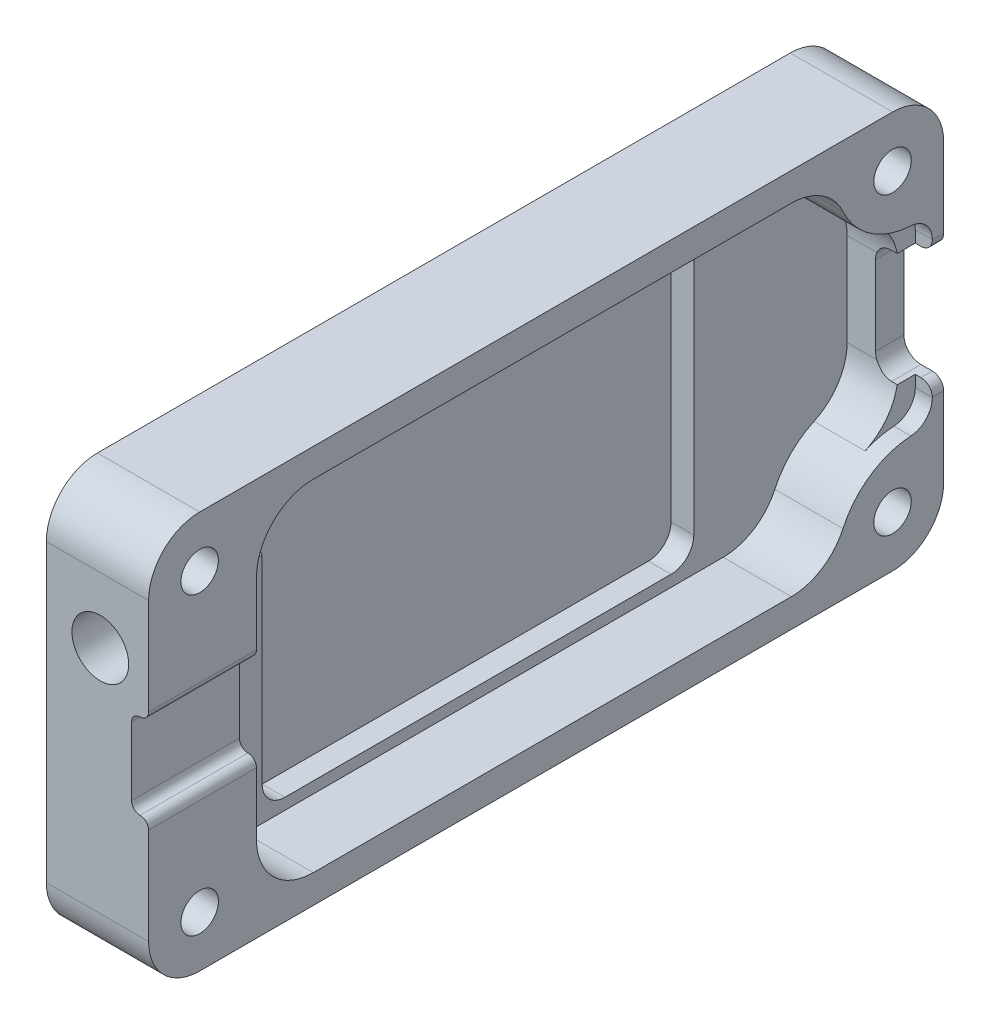
SolidWorks part; units mm, degrees
ref_plane "Front Plane" through (0, 0, 0) normal (0, 0, 1) x (1, 0, 0)
ref_plane "Top Plane" through (0, 0, 0) normal (0, 1, 0) x (1, 0, 0)
ref_plane "Right Plane" through (0, 0, 0) normal (1, 0, 0) x (0, 0, -1)
sketch "Sketch3" plane through (0, 0, 0) normal (1, 0, 0) x (0, 0, -1)
  line L1 (-35, -17.5) -> (35, -17.5)
  line L2 (-35, -17.5) -> (-35, 17.5)
  line L3 (-35, 17.5) -> (35, 17.5)
  line L4 (35, -17.5) -> (35, 17.5)
  line L5 (-35, -17.5) -> (35, 17.5) construction
  line L6 (-35, 17.5) -> (35, -17.5) construction
  point P0 (0, 0)
  dimension "D1" = 70
  dimension "D2" = 35
extrude "Boss-Extrude2" add sketch "Sketch3" along normal blind 3
sketch "Sketch4" plane through (3, 0, 0) normal (1, 0, 0) x (0, 0, -1)
  line L0 (35, 17.5) -> (-35, 17.5) construction
  line L1 (-35, -17.5) -> (35, -17.5)
  line L2 (-35, -17.5) -> (-35, 17.5)
  line L3 (-35, 17.5) -> (35, 17.5)
  line L4 (35, -17.5) -> (35, 17.5)
  line L5 (-35, -17.5) -> (35, 17.5) construction
  line L6 (-35, 17.5) -> (35, -17.5) construction
  line L8 (-32.5, -15) -> (32.5, -15)
  line L9 (-32.5, -15) -> (-32.5, 15)
  line L10 (-32.5, 15) -> (32.5, 15)
  line L11 (32.5, -15) -> (32.5, 15)
  line L12 (-32.5, -15) -> (32.5, 15) construction
  line L13 (-32.5, 15) -> (32.5, -15) construction
  point P0 (0, 0)
  point P8 (0, 0)
  dimension "D1" = 30
  dimension "D2" = 65
  dimension "D3" = 70
extrude "Boss-Extrude3" add sketch "Sketch4" along normal blind 6
sketch "Sketch6" plane through (3, 0, 0) normal (1, 0, 0) x (0, 0, -1)
  line L1 (-32.5, 15) -> (-32.5, -15) construction
  line L2 (32.5, 15) -> (-32.5, 15) construction
  line L3 (-25.5, 15) -> (-32.5, 15)
  line L4 (-32.5, 15) -> (-32.5, 8)
  line L5 (-32.5, -15) -> (32.5, -15) construction
  line L6 (32.5, -15) -> (32.5, 15) construction
  line L7 (-32.5, 15) -> (-32.5, -15) construction
  line L8 (-32.5, -8) -> (-32.5, -15)
  line L9 (-32.5, -15) -> (-25.5, -15)
  line L10 (-32.5, -15) -> (32.5, -15) construction
  line L11 (32.5, 8) -> (32.5, 15)
  line L12 (32.5, 15) -> (25.5, 15)
  line L13 (32.5, -8) -> (32.5, -15)
  line L14 (32.5, -15) -> (25.5, -15)
  arc A0 (-32.5, 8) -> (-25.5, 15) centre (-32.5, 15) ccw
  arc A1 (-32.5, -8) -> (-25.5, -15) centre (-32.5, -15) cw
  arc A2 (32.5, -8) -> (25.5, -15) centre (32.5, -15) ccw
  arc A3 (25.5, 15) -> (32.5, 8) centre (32.5, 15) ccw
  dimension "D1" = 7
extrude "Boss-Extrude4" add sketch "Sketch6" along normal blind 6
sketch "Sketch7" plane through (3, 0, 0) normal (1, 0, 0) x (0, 0, -1)
  line L1 (-19, -14) -> (19, -14)
  line L2 (-19, -14) -> (-19, 14)
  line L3 (-19, 14) -> (19, 14)
  line L4 (19, -14) -> (19, 14)
  line L5 (-19, -14) -> (19, 14) construction
  line L6 (-19, 14) -> (19, -14) construction
  point P0 (0, 0)
  dimension "D1" = 38
  dimension "D2" = 28
extrude "Cut-Extrude1" cut sketch "Sketch7" against normal blind 2
sketch "Sketch17" plane through (3, 0, 0) normal (1, 0, 0) x (0, 0, -1)
  line L1 (-25.5, -15) -> (-32.5, -15)
  line L2 (-25.5, -15) -> (-25.5, 15)
  line L3 (-25.5, 15) -> (-32.5, 15)
  line L4 (-32.5, -15) -> (-32.5, 15)
extrude "Boss-Extrude6" add sketch "Sketch17" along normal up to surface (6 mm away) up to face at (9, 0, 0)
sketch "Sketch8" plane through (9, 0, 0) normal (1, 0, 0) x (0, 0, -1)
  line L0 (-35, 17.5) -> (-35, -17.5) construction
  line L1 (-35, -17.5) -> (35, -17.5) construction
  line L2 (35, 17.5) -> (-35, 17.5) construction
  line L3 (35, -17.5) -> (35, 17.5) construction
  circle A0 centre (-30.5, 13) radius 1.65
  circle A1 centre (30.5, 13) radius 1.65
  circle A2 centre (30.5, -13) radius 1.65
  circle A3 centre (-30.5, -13) radius 1.65
  dimension "D3" = 3.3
  dimension "D6" = 4.5
  dimension "D1" = 4.5
  dimension "D2" = 4.5
  dimension "D4" = 4.5
  dimension "D5" = 4.5
  dimension "D7" = 4.5
  dimension "D8" = 4.5
  dimension "D9" = 4.5
extrude "Cut-Extrude2" cut sketch "Sketch8" against normal up to surface (9 mm away) up to face at (0, 0, 0)
fillet "Fillet1" radius 4.5 4 edges at (4.5, -17.5, -35) (4.5, 17.5, -35) (4.5, 17.5, 35) (4.5, -17.5, 35)
sketch "Sketch9" plane through (9, 0, 0) normal (1, 0, 0) x (0, 0, -1)
  line L0 (32.5, -8) -> (32.5, 8) construction
  line L1 (32.5, 5) -> (35, 5)
  line L2 (32.5, 5) -> (32.5, -5)
  line L3 (32.5, -5) -> (35, -5)
  line L4 (35, 5) -> (35, -5)
  line L5 (35, -13) -> (35, 13) construction
  line L6 (30.5, 17.5) -> (-30.5, 17.5) construction
  line L7 (-30.5, -17.5) -> (30.5, -17.5) construction
  dimension "D1" = 12.5
  dimension "D2" = 12.5
extrude "Cut-Extrude3" cut sketch "Sketch9" against normal blind 3.5
sketch "Sketch10" plane through (9, 0, 0) normal (1, 0, 0) x (0, 0, -1)
  line L1 (32.5, 8) -> (34, 8)
  line L2 (32.5, 8) -> (32.5, -8)
  line L3 (32.5, -8) -> (34, -8)
  line L4 (34, 8) -> (34, -8)
  point P7 (32.5, -8)
  dimension "D1" = 1.5
extrude "Cut-Extrude4" cut sketch "Sketch10" against normal blind 1.5
fillet "Fillet2" radius 1 2 edges at (9, -5, -34.5) (9, 5, -34.5)
fillet "Fillet3" radius 1.5 2 edges at (5.5, 5, -33.75) (5.5, -5, -33.75)
sketch "Sketch11" plane through (0, 0, 0) normal (-1, 0, 0) x (0, 0, 1)
  circle A1 centre (30.5, 13) radius 3
  circle A2 centre (30.5, -13) radius 3
  circle A3 centre (-30.5, -13) radius 3
  circle A4 centre (-30.5, 13) radius 3
  dimension "D1" = 6
extrude "Cut-Extrude5" cut sketch "Sketch11" against normal blind 1.8
sketch "Sketch12" plane through (9, 0, 0) normal (1, 0, 0) x (0, 0, -1)
  line L0 (-35, 13) -> (-35, -13) construction
  line L1 (-35, 3.75) -> (-25.5, 3.75)
  line L2 (-35, 3.75) -> (-35, -3.75)
  line L3 (-35, -3.75) -> (-25.5, -3.75)
  line L4 (-25.5, 3.75) -> (-25.5, -3.75)
  line L6 (30.5, 17.5) -> (-30.5, 17.5) construction
  line L7 (-30.5, -17.5) -> (30.5, -17.5) construction
  line L8 (-25.5, -15) -> (-25.5, 15) construction
  point P6 (-25.5, -3.75)
  dimension "D1" = 13.75
  dimension "D2" = 13.75
extrude "Cut-Extrude6" cut sketch "Sketch12" against normal blind 1.5
fillet "Fillet4" radius 0.75 8 edges at (8.25, -3.75, 35) (7.5, 3.75, 30.25) (8.25, 3.75, 35) (8.25, 3.75, 25.5) (7.5, -3.75, 30.25) (8.25, -3.75, 25.5) (9, -3.75, 30.25) (9, 3.75, 30.25)
chamfer "Chamfer1" distance 1.8 angle 45 4 edges at (1.8, 13, 33.5) (1.8, -13, 33.5) (1.8, -13, -27.5) (1.8, 13, -27.5)
sketch "Sketch13" plane through (0, 0, 35) normal (0, 0, 1) x (1, 0, 0)
  line L0 (0, 13) -> (0, -13) construction
  line L1 (9, 13) -> (0, 13) construction
  circle A0 centre (4.75, 7.25) radius 2.5
  dimension "D1" = 5
  dimension "D2" = 4.75
  dimension "D3" = 5.75
fillet "Fillet5" radius 5 4 edges at (5.25, 8, -32.5) (5.25, -8, -32.5) (6, -15, -25.5) (6, 15, -25.5)
extrude "Cut-Extrude8" cut sketch "Sketch13" against normal blind 22 contours A0
fillet "Fillet6" radius 5 2 edges at (6, -15, 25.5) (6, 15, 25.5)
fillet "Fillet7" radius 2 4 edges at (2, -14, 19) (2, -14, -19) (2, 14, -19) (2, 14, 19)
fillet "Fillet8" radius 2 2 edges at (8.25, -8, -34) (8.25, 8, -34)
